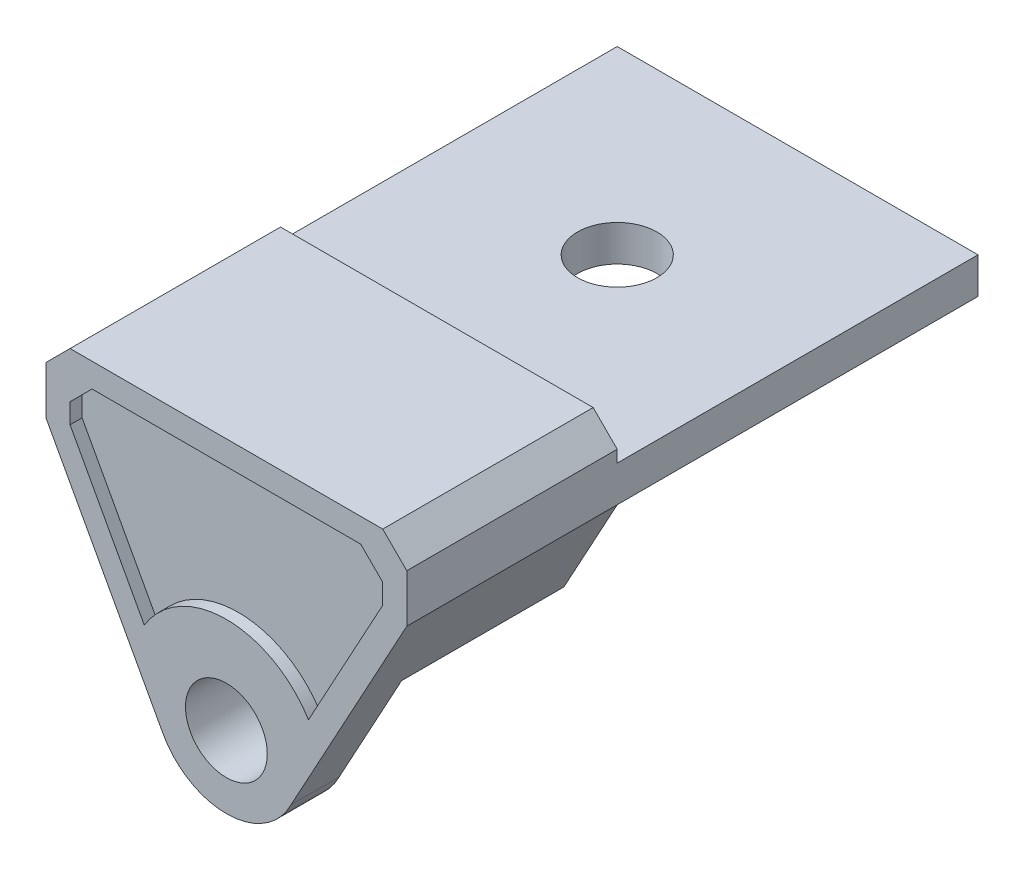
SolidWorks part; units mm, degrees
note: The reader was unsure of these and kept them because the rebuilt part matched: shared geometry of "Sketch1<3>".
ref_plane "Front Plane" through (0, 0, 0) normal (0, 0, 1) x (1, 0, 0)
ref_plane "Top Plane" through (0, 0, 0) normal (0, 1, 0) x (1, 0, 0)
ref_plane "Right Plane" through (0, 0, 0) normal (1, 0, 0) x (0, 0, -1)
sketch "Sketch1" plane through (0, 0, 0) normal (0, 0, 1) x (1, 0, 0)
  line L0 (4.5962, 4.5962) -> (5.3033, 5.3033) construction
  line L1 (-4.5962, 4.5962) -> (-5.3033, 5.3033) construction
  line L2 (4.5962, 4.5962) -> (5.3033, 5.3033)
  line L3 (-4.5962, 4.5962) -> (-5.3033, 5.3033)
  line L4 (4.5941, 4.8769) -> (5.1619, 5.4447)
  line L5 (-4.5941, 4.8769) -> (-5.1619, 5.4447)
  line L6 (-4.5962, 4.5962) -> (-4.4548, 4.4548)
  line L8 (4.5962, 4.5962) -> (4.4548, 4.4548)
  circle A2 centre (0, 0) radius 7.5
  arc A4 (4.5941, 4.8769) -> (-4.5941, 4.8769) centre (0, 0) ccw
  circle A5 centre (0, 0) radius 6.3
  arc A7 (4.5962, 4.5962) -> (-4.5962, 4.5962) centre (0, 0) ccw construction
  dimension "D1" = 0.2
  dimension "D2" = 12.6
extrude "Boss-Extrude1" add sketch "Sketch1" against normal up to surface (2 mm away) contours A4 L4 A2 L5
extrude "Boss-Extrude2" add sketch "Sketch1<3>" along normal blind 4.75 contours A4 L4 A2 L5 | A5 L8 L2 A2 L4 A4 L5 L3 L6
sketch "Sketch1<3>" plane through (0, 0, 0) normal (0, 0, 1) x (1, 0, 0) same geometry as "Sketch1"
sketch "Sketch3" plane through (0, 0, 4.75) normal (0, 0, 1) x (1, 0, 0)
  line L0 (-5.3033, 5.3033) -> (-2.7928, -1.0957)
  line L1 (5.3033, 5.3033) -> (2.7928, -1.0957)
  line L2 (2.9062, 4.6695) -> (1.9639, 2.2678)
  line L3 (-2.9062, 4.6695) -> (-1.9639, 2.2678)
  line L4 (-2.9062, 4.6695) -> (-0.9309, -0.3652) construction
  line L5 (2.9062, 4.6695) -> (0.9309, -0.3652) construction
  circle A0 centre (0, 0) radius 3
  circle A1 centre (0, 0) radius 1.7 construction
  arc A2 (5.3033, 5.3033) -> (-5.3033, 5.3033) centre (0, 0) ccw construction
  arc A3 (5.3033, 5.3033) -> (-5.3033, 5.3033) centre (0, 0) ccw
  arc A4 (2.9062, 4.6695) -> (-2.9062, 4.6695) centre (0, 0) ccw
  circle A6 centre (0, 0) radius 1.7
  dimension "D1" = 6
  dimension "D2" = 2
extrude "Boss-Extrude3" add sketch "Sketch3" along normal blind 2
sketch "Sketch4" plane through (0, 0, 4.75) normal (0, 0, -1) x (-1, 0, 0)
  circle A2 centre (0, 0) radius 2.2
  circle A3 centre (0, 0) radius 2.2
  circle M6 centre (0, 0) radius 1.7
  dimension "D1" = 0.5
extrude "Boss-Extrude4" add sketch "Sketch4" along normal blind 0.5 contours A3 M6
chamfer "Chamfer1" distance 0.5 angle 45 1 edges at (2.2, 0, 4.75)
sketch "Sketch5" plane through (0, 0, 6.75) normal (0, 0, 1) x (1, 0, 0)
  line L0 (0, 10.5) -> (0, 7.5) construction
  line L1 (-7.5, 10.5) -> (7.5, 10.5)
  line L2 (-7.5, 10.5) -> (-7.5, 7.5)
  line L3 (-7.5, 7.5) -> (7.5, 7.5)
  line L4 (7.5, 10.5) -> (7.5, 7.5)
  line L5 (-7.5, 7.5) -> (-2.6347, -1.4347)
  line L6 (7.5, 7.5) -> (2.5835, -1.525)
  arc A0 (-2.7928, -1.0957) -> (2.7928, -1.0957) centre (0, 0) ccw construction
  arc A1 (5.3033, 5.3033) -> (-5.3033, 5.3033) centre (0, 0) ccw construction
  arc A2 (-2.7928, -1.0957) -> (2.7928, -1.0957) centre (0, 0) ccw
  line M12 (2.7928, -1.0957) -> (5.3033, 5.3033)
  arc M13 (5.3033, 5.3033) -> (-5.3033, 5.3033) centre (0, 0) ccw
  line M14 (-5.3033, 5.3033) -> (-2.7928, -1.0957)
  arc M15 (-2.7928, -1.0957) -> (2.7928, -1.0957) centre (0, 0) ccw
  dimension "D1" = 15
  dimension "D2" = 3
extrude "Boss-Extrude5" add sketch "Sketch5" against normal up to surface (2 mm away) contours L3 L5 M15 M14 M13 | L0 L1 L2 L3 | L1 L0 L3 L4 | L6 L3 M13 M12 M15
sketch "Sketch6" plane through (0, 0, 4.75) normal (0, 0, -1) x (-1, 0, 0)
  line L0 (-2.6823, -1.3436) -> (-7.5, 7.5)
  line L1 (2.6347, -1.4347) -> (7.5, 7.5)
  arc A0 (5.4997, 3.8266) -> (-5.4992, 3.8273) centre (0, 0) ccw
  arc A1 (5.922, 4.6022) -> (-5.9216, 4.6027) centre (0, 0) ccw
extrude "Boss-Extrude6" add sketch "Sketch6" along normal up to surface (6.75 mm away)
sketch "Sketch8" plane through (0, 0, 4.75) normal (0, 0, -1) x (-1, 0, 0)
  line L5 (5.922, 4.6022) -> (7.5, 7.5)
  line L6 (7.5, 7.5) -> (7.5, 10.5)
  line L7 (7.5, 10.5) -> (-7.5, 10.5)
  line L8 (-7.5, 10.5) -> (-7.5, 7.5)
  line L9 (-7.5, 7.5) -> (-5.9216, 4.6027)
  line L10 (5.922, 4.6022) -> (7.5, 7.5)
  line L11 (7.5, 7.5) -> (7.5, 10.5)
  line L12 (7.5, 10.5) -> (-7.5, 10.5)
  line L13 (-7.5, 10.5) -> (-7.5, 7.5)
  line L14 (-7.5, 7.5) -> (-5.9216, 4.6027)
  arc A1 (5.922, 4.6022) -> (-5.9216, 4.6027) centre (0, 0) ccw
  arc A2 (5.922, 4.6022) -> (-5.9216, 4.6027) centre (0, 0) ccw
  dimension "D1" = 0
extrude "Boss-Extrude8" add sketch "Sketch8" along normal up to surface (6.75 mm away) up to face at (0, 6.1299, -2)
sketch "Sketch10" plane through (0, 0, -2) normal (0, 0, -1) x (-1, 0, 0)
  line L1 (-7.5, 10.5) -> (7.5, 10.5)
  line L2 (-7.5, 10.5) -> (-7.5, 7.5)
  line L3 (-7.5, 7.5) -> (7.5, 7.5)
  line L4 (7.5, 10.5) -> (7.5, 7.5)
extrude "Boss-Extrude9" add sketch "Sketch10" along normal blind 15
sketch "Sketch11" plane through (0, 7.5, 0) normal (0, -1, 0) x (1, 0, 0)
  line L3 (0, -17) -> (0, -9.5) construction
  line L4 (7.5, -17) -> (-7.5, -17) construction
  circle A0 centre (0, -9.5) radius 1.65
  dimension "D1" = 3.3
  dimension "D2" = 7.5
extrude "Cut-Extrude1" cut sketch "Sketch11" against normal through all
fillet "Fillet1" radius 0.2 2 edges at (-5.4997, 3.8266, 1.375) (5.4992, 3.8273, 1.375)
chamfer "Chamfer6" distance 1.5 angle 45 2 edges at (-7.5, 10.5, -5.125) (7.5, 10.5, -5.125)
sketch "Sketch12" plane through (0, 0, -2) normal (0, 0, -1) x (-1, 0, 0)
  line L0 (-5.6501, 4.1043) -> (-5.2835, 3.4314)
  line L1 (5.6506, 4.1037) -> (5.284, 3.4306)
  line L7 (5.6506, 4.1037) -> (7.5, 7.5)
  line L8 (7.5, 7.5) -> (-7.5, 7.5)
  line L9 (-7.5, 7.5) -> (-5.6501, 4.1043)
  line L10 (-4.7376, 4.7376) -> (-5.3033, 5.3033)
  line L11 (-5.16, 5.4428) -> (-4.5941, 4.8769)
  line L12 (4.5941, 4.8769) -> (5.16, 5.4428)
  line L13 (5.3033, 5.3033) -> (4.7376, 4.7376)
  line L14 (5.6506, 4.1037) -> (7.5, 7.5)
  line L15 (7.5, 7.5) -> (-7.5, 7.5)
  line L16 (-7.5, 7.5) -> (-5.6501, 4.1043)
  line L17 (-4.7376, 4.7376) -> (-5.3033, 5.3033)
  line L18 (-5.16, 5.4428) -> (-4.5941, 4.8769)
  line L19 (4.5941, 4.8769) -> (5.16, 5.4428)
  line L20 (5.3033, 5.3033) -> (4.7376, 4.7376)
  arc A0 (5.284, 3.4306) -> (-5.2835, 3.4314) centre (0, 0) ccw
  arc A1 (5.853, 4.4755) -> (-5.8526, 4.476) centre (0, 0) ccw
  arc A9 (5.3163, 4.0777) -> (4.7376, 4.7376) centre (0, 0) ccw
  arc A10 (5.3163, 4.0777) -> (5.6506, 4.1037) centre (5.475, 4.1994) ccw
  arc A11 (-5.6501, 4.1043) -> (-5.3158, 4.0782) centre (-5.4745, 4.2) ccw
  arc A12 (-4.7376, 4.7376) -> (-5.3158, 4.0782) centre (0, 0) ccw
  arc A13 (-5.16, 5.4428) -> (-5.3033, 5.3033) centre (0, 0) ccw
  arc A14 (4.5941, 4.8769) -> (-4.5941, 4.8769) centre (0, 0) ccw
  arc A15 (5.3033, 5.3033) -> (5.16, 5.4428) centre (0, 0) ccw
  arc A16 (5.3163, 4.0777) -> (4.7376, 4.7376) centre (0, 0) ccw
  arc A17 (5.3163, 4.0777) -> (5.6506, 4.1037) centre (5.475, 4.1994) ccw
  arc A18 (-5.6501, 4.1043) -> (-5.3158, 4.0782) centre (-5.4745, 4.2) ccw
  arc A19 (-4.7376, 4.7376) -> (-5.3158, 4.0782) centre (0, 0) ccw
  arc A20 (-5.16, 5.4428) -> (-5.3033, 5.3033) centre (0, 0) ccw
  arc A21 (4.5941, 4.8769) -> (-4.5941, 4.8769) centre (0, 0) ccw
  arc A22 (5.3033, 5.3033) -> (5.16, 5.4428) centre (0, 0) ccw
  arc M1 (4.7376, 4.7376) -> (5.3163, 4.0777) centre (0, 0) cw
  arc M2 (5.3163, 4.0777) -> (5.6506, 4.1037) centre (5.475, 4.1994) ccw
  line M3 (5.6506, 4.1037) -> (7.5, 7.5)
  arc M6 (-5.6501, 4.1043) -> (-5.3158, 4.0782) centre (-5.4745, 4.2) ccw
  arc M7 (-5.3158, 4.0782) -> (-4.7376, 4.7376) centre (0, 0) cw
  line M8 (-4.7376, 4.7376) -> (-5.3033, 5.3033)
  arc M9 (-5.3033, 5.3033) -> (-5.16, 5.4428) centre (0, 0) cw
  line M10 (-5.16, 5.4428) -> (-4.5941, 4.8769)
  arc M11 (-4.5941, 4.8769) -> (4.5941, 4.8769) centre (0, 0) cw
  line M12 (4.5941, 4.8769) -> (5.16, 5.4428)
  arc M13 (5.16, 5.4428) -> (5.3033, 5.3033) centre (0, 0) cw
  line M14 (5.3033, 5.3033) -> (4.7376, 4.7376)
  dimension "D1" = 12.6
  dimension "D2" = 0
extrude "Boss-Extrude11" add sketch "Sketch12" against normal up to surface (6.75 mm away) contours A1 L17 M10 M9 | L20 A1 L18 L0 A0 L1 M12 M11 M8 M7 M6 M2 M1 | A1 L16 M8 M6 M7 | A1 L19 M14 M13 | A1 L20 M3 M1 M2 up to face at (0.0074, 3.2043, 4.75)
sketch "Sketch13" plane through (0, 0, 6.75) normal (0, 0, 1) x (1, 0, 0)
  line L0 (-6.5, 7.7546) -> (-3.4131, 2.0858)
  line L1 (-6.5, 8.5858) -> (-6.5, 7.7546)
  line L2 (-5.5858, 9.5) -> (-6.5, 8.5858)
  line L3 (5.5858, 9.5) -> (-5.5858, 9.5)
  line L4 (6.5, 8.5858) -> (5.5858, 9.5)
  line L5 (6.5, 7.7547) -> (6.5, 8.5858)
  line L6 (3.4124, 2.087) -> (6.5, 7.7547)
  line L7 (6, 10.5) -> (-6, 10.5)
  line L8 (-6, 10.5) -> (-7.5, 9)
  line L9 (-7.5, 9) -> (-7.5, 7.5)
  line L10 (-7.5, 7.5) -> (-2.6347, -1.4347)
  line L11 (2.6823, -1.3436) -> (7.5, 7.5)
  line L12 (7.5, 7.5) -> (7.5, 9)
  line L13 (7.5, 9) -> (6, 10.5)
  line L14 (6, 10.5) -> (-6, 10.5)
  line L15 (-6, 10.5) -> (-7.5, 9)
  line L16 (-7.5, 9) -> (-7.5, 7.5)
  line L17 (-7.5, 7.5) -> (-2.6347, -1.4347)
  line L18 (2.6823, -1.3436) -> (7.5, 7.5)
  line L19 (7.5, 7.5) -> (7.5, 9)
  line L20 (7.5, 9) -> (6, 10.5)
  arc A1 (2.6823, -1.3436) -> (-2.6347, -1.4347) centre (0, 0) ccw
  arc A2 (3.4124, 2.087) -> (-3.4131, 2.0858) centre (0, 0) ccw
  arc A3 (-2.6347, -1.4347) -> (2.6823, -1.3436) centre (0, 0) ccw
  dimension "D1" = 0
  dimension "D2" = 1
sketch "Sketch16" plane through (0, 0, -17) normal (0, 0, -1) x (-1, 0, 0)
  line L0 (-7.5, 9) -> (-7.5, 10.5)
  line L1 (7.5, 9) -> (-7.5, 9)
  line L2 (7.5, 9) -> (7.5, 10.5)
  line L3 (7.5, 10.5) -> (-7.5, 10.5)
extrude "Boss-Extrude12" add sketch "Sketch16" against normal up to surface (23.75 mm away) up to face at (0.0094, 6.2014, 6.75)
extrude "Cut-Extrude3" cut sketch "Sketch13" against normal blind 0.5 contours A2 L6 L5 L4 L3 L2 L1 L0
sketch "Sketch17" plane through (0, 0, -17) normal (0, 0, -1) x (-1, 0, 0)
  line L0 (7.5, 10.5) -> (-7.5, 10.5) construction
  line L1 (-7.5, 10.5) -> (7.5, 10.5)
  line L2 (-7.5, 10.5) -> (-7.5, 9)
  line L3 (-7.5, 9) -> (7.5, 9)
  line L4 (7.5, 10.5) -> (7.5, 9)
  line L5 (7.5, 7.5) -> (7.5, 10.5) construction
  dimension "D1" = 15
extrude "Cut-Extrude4" cut sketch "Sketch17" against normal up to surface (15 mm away) up to face at (-0.0002, 6.1827, -2)
chamfer "Chamfer8" distance 1 angle 45 2 edges at (-7.5, 10.5, 2.375) (7.5, 10.5, 2.375)
